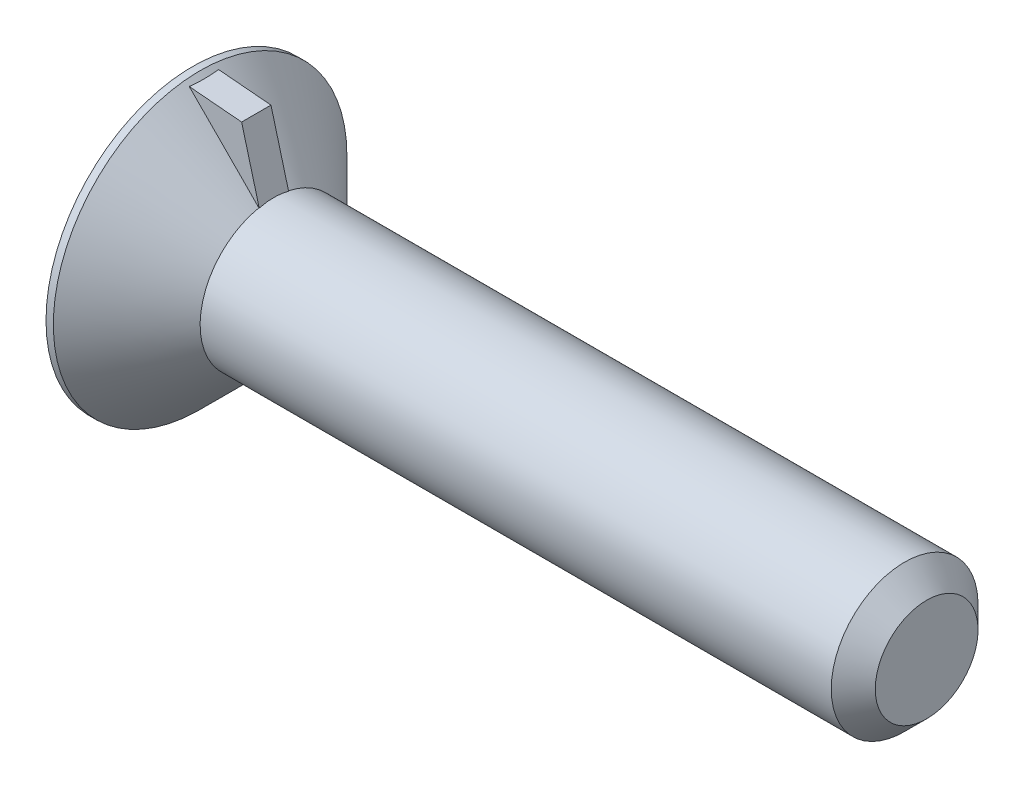
SolidWorks part; units mm, degrees
ref_plane "Front Plane" through (0, 0, 0) normal (0, 0, 1) x (1, 0, 0)
ref_plane "Top Plane" through (0, 0, 0) normal (0, 1, 0) x (1, 0, 0)
ref_plane "Right Plane" through (0, 0, 0) normal (1, 0, 0) x (0, 0, -1)
sketch "BaseBodySke" plane through (0, 0, 0) normal (0, 0, 1) x (1, 0, 0)
  line L0 (-107.4075, 0) -> (214.0904, 0) construction
  line L1 (0, 0) -> (0, 10)
  line L2 (0, 10) -> (0.5, 10)
  line L3 (0.5, 10) -> (5.5, 5)
  line L4 (5.5, 5) -> (50, 5)
  line L5 (50, 5) -> (50, 0)
  line L6 (50, 0) -> (0, 0)
  line L7 (24, 10) -> (24, -17.9005) construction
  line L8 (34.0602, 4.3095) -> (57.5082, 4.3095) construction
  line L9 (48.75, 13.8049) -> (48.75, -14.5195) construction
  dimension "Thread_length" = 26
  dimension "Length" = 50
revolve "BaseBody" add sketch "BaseBodySke" angle 360 about L6
cosmetic thread "ThreadCosmetic" [suppressed] parameters "Thread_length"=26, "Thread_minor"=8.619
sketch "FlatEndSke" plane through (0, 0, 0) normal (0, 0, 1) x (1, 0, 0)
  line L0 (48.5, 5) -> (50, 5)
  line L1 (50, 5) -> (50, 3.5)
  line L2 (50, 3.5) -> (48.5, 5)
  line L3 (50, -5) -> (50, 5) construction
  line L4 (50, 5) -> (5.5, 5) construction
  line L5 (0, 0) -> (89.7899, 0) construction
  dimension "D1" = 45
revolve "FlatEnd" cut sketch "FlatEndSke" angle 360 about L5
sketch "CutEndSke" plane through (50, 0, 0) normal (1, 0, 0) x (0, 0, -1)
  circle A0 centre (0, 0) radius 5 construction
  circle A1 centre (0, 0) radius 5
extrude "CutEnd" [suppressed] cut sketch "CutEndSke" against normal blind 1.5
dome "RoundEnd" [suppressed] faces to dome 1 distance 1.5 parameters "D1"=1.5
sketch "ThdSchSke" plane through (0, 0, 0) normal (0, 0, 1) x (1, 0, 0)
  line L0 (0, 0) -> (89.8666, 0) construction
  line L1 (50, -27.1828) -> (50, 30.5493) construction
  line L2 (47.75, 4.3095) -> (47.3513, 5)
  line L3 (47.3513, 5) -> (47.3513, 5.7973)
  line L4 (47.3513, 5.7973) -> (48.1487, 5.7973)
  line L5 (48.1487, 5.7973) -> (48.1487, 5)
  line L6 (48.1487, 5) -> (47.75, 4.3095)
  dimension "Length" = 50
  dimension "Advance" = 2.25
  dimension "D1" = 8.619
  dimension "D2" = 10
revolve "ThreadSchematic" [suppressed] cut sketch "ThdSchSke" angle 360 about L0
pattern_linear "ThdSchPat" [suppressed] count 20 spacing 1.25 along (-1, 0, 0) of bodies 105
sketch "KeySke" plane through (0, 0, 0) normal (0, 0, 1) x (1, 0, 0)
  line L0 (0, 9.7561) -> (0, 0)
  line L1 (0, 0) -> (6.8397, 0)
  line L2 (6.8397, 0) -> (4.327, 9.3775)
  line L3 (4.327, 9.3775) -> (0, 9.7561)
  line L4 (6.8397, 0) -> (6.8397, 17.2209) construction
  line L5 (0, 9.7561) -> (9.5811, 9.7561) construction
  dimension "D1" = 5
  dimension "D2" = 15
  dimension "D3" = 9.7561
extrude "Key" add sketch "KeySke" along normal mid plane 2
equation "\"Thread_minor@ThreadCosmetic\" = \"Minor_dia@BaseBodySke\""
equation "\"Thread_length@ThreadCosmetic\" = \"Thread_length@BaseBodySke\""
equation "\"D1@CutEnd\" = \"Chamfer_width@FlatEndSke\""
equation "\"D1@RoundEnd\" = \"Chamfer_width@FlatEndSke\""
equation "\"Length@ThdSchSke\" = \"Length@BaseBodySke\""
equation "\"Advance@ThdSchSke\" = \"Advance@BaseBodySke\" * 1.8"
equation "\"D2@ThdSchSke\" = \"Diameter@BaseBodySke\""
equation "\"D1@ThdSchSke\" = \"Minor_dia@BaseBodySke\""
equation "\"D3@ThdSchPat\" = \"Advance@BaseBodySke\""
equation "\"D1@ThdSchPat\" =  int( \"Thread_length@BaseBodySke\" / \"Advance@BaseBodySke\" ) "
equation "\"D3@KeySke\" = \"Head_diameter@BaseBodySke\" / 2.05"
equation "\"Key_thickness@Key\" = \"Diameter@BaseBodySke\"/5"
